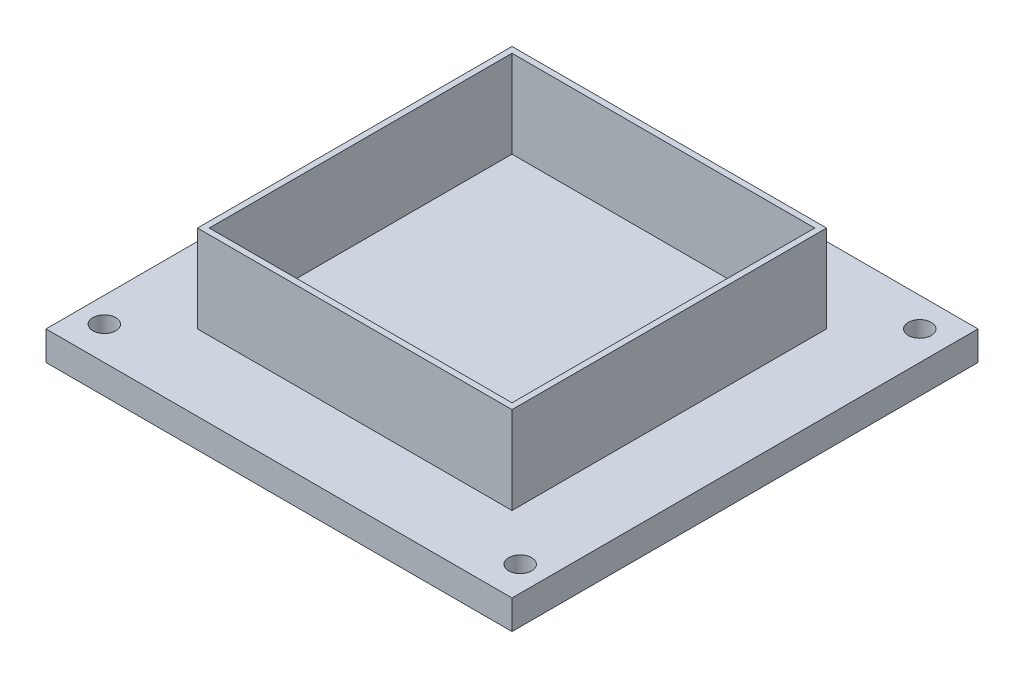
SolidWorks part; units mm, degrees
material "ABS_rapid_prototype"
ref_plane "Front" through (0, 0, 0) normal (0, 0, 1) x (1, 0, 0)
ref_plane "Top" through (0, 0, 0) normal (0, 1, 0) x (1, 0, 0)
ref_plane "Right" through (0, 0, 0) normal (1, 0, 0) x (0, 0, -1)
sketch "Sketch1" plane through (0, 0, 0) normal (0, 1, 0) x (1, 0, 0)
  line L1 (-50.8, 50.8) -> (50.8, 50.8)
  line L2 (-50.8, 50.8) -> (-50.8, -50.8)
  line L3 (-50.8, -50.8) -> (50.8, -50.8)
  line L4 (50.8, 50.8) -> (50.8, -50.8)
  line L5 (-50.8, 50.8) -> (50.8, -50.8) construction
  line L6 (-50.8, -50.8) -> (50.8, 50.8) construction
  line L7 (-38.1, 38.1) -> (38.1, 38.1)
  line L8 (-38.1, 38.1) -> (-38.1, -38.1)
  line L9 (-38.1, -38.1) -> (38.1, -38.1)
  line L10 (38.1, 38.1) -> (38.1, -38.1)
  line L11 (-38.1, 38.1) -> (38.1, -38.1) construction
  line L12 (-38.1, -38.1) -> (38.1, 38.1) construction
  line L13 (-34.29, 34.29) -> (34.29, 34.29)
  line L14 (-34.29, 34.29) -> (-34.29, -34.29)
  line L15 (-34.29, -34.29) -> (34.29, -34.29)
  line L16 (34.29, 34.29) -> (34.29, -34.29)
  line L17 (-34.29, 34.29) -> (34.29, -34.29) construction
  line L18 (-34.29, -34.29) -> (34.29, 34.29) construction
  line L19 (-33, 33) -> (33, 33)
  line L20 (-33, 33) -> (-33, -33)
  line L21 (-33, -33) -> (33, -33)
  line L22 (33, 33) -> (33, -33)
  line L23 (-33, 33) -> (33, -33) construction
  line L24 (-33, -33) -> (33, 33) construction
  point P0 (0, 0)
  point P5 (0, 0)
  point P11 (0, 0)
  point P16 (0, 0)
  dimension "D1" = 101.6
  dimension "D2" = 76.2
  dimension "D3" = 68.58
  dimension "D4" = 66
extrude "Boss-Extrude1" add sketch "Sketch1" along normal blind 25.4 contours L16 L13 L14 L15 L19 L22 L21 L20 region at (0, 0, -33.3201)
sketch "Sketch2" plane through (0, 0, 0) normal (0, 1, 0) x (1, 0, 0)
  line L1 (-50.8, 50.8) -> (50.8, 50.8)
  line L2 (-50.8, 50.8) -> (-50.8, -50.8)
  line L3 (-50.8, -50.8) -> (50.8, -50.8)
  line L4 (50.8, 50.8) -> (50.8, -50.8)
  line L5 (-50.8, 50.8) -> (50.8, -50.8) construction
  line L6 (-50.8, -50.8) -> (50.8, 50.8) construction
  line L7 (-34.29, -34.29) -> (34.29, -34.29)
  line L8 (-34.29, -34.29) -> (-34.29, 34.29)
  line L9 (-34.29, 34.29) -> (34.29, 34.29)
  line L10 (34.29, -34.29) -> (34.29, 34.29)
  line L11 (-34.29, -34.29) -> (34.29, 34.29) construction
  line L12 (-34.29, 34.29) -> (34.29, -34.29) construction
  point P0 (0, 0)
  point P5 (0, 0)
extrude "Boss-Extrude2" add sketch "Sketch2" along normal blind 6.35 contours L2 L1 L4 L3
sketch "Sketch3" plane through (0, 6.35, 0) normal (0, 1, 0) x (1, 0, 0)
  line L0 (-50.8, 50.8) -> (50.8, 50.8) construction
  line L1 (-50.8, 50.8) -> (-50.8, -50.8) construction
  line L2 (0, 0) -> (0, 60.2924) construction
  circle A0 centre (-44.45, 44.45) radius 2.5
  circle A1 centre (-45.3318, -43.5504) radius 2.5
  circle A2 centre (45.3318, -43.5504) radius 2.5
  circle A3 centre (44.45, 44.45) radius 2.5
  dimension "D1" = 5
  dimension "D2" = 6.35
  dimension "D3" = 6.35
extrude "Cut-Extrude1" cut sketch "Sketch3" against normal through all
